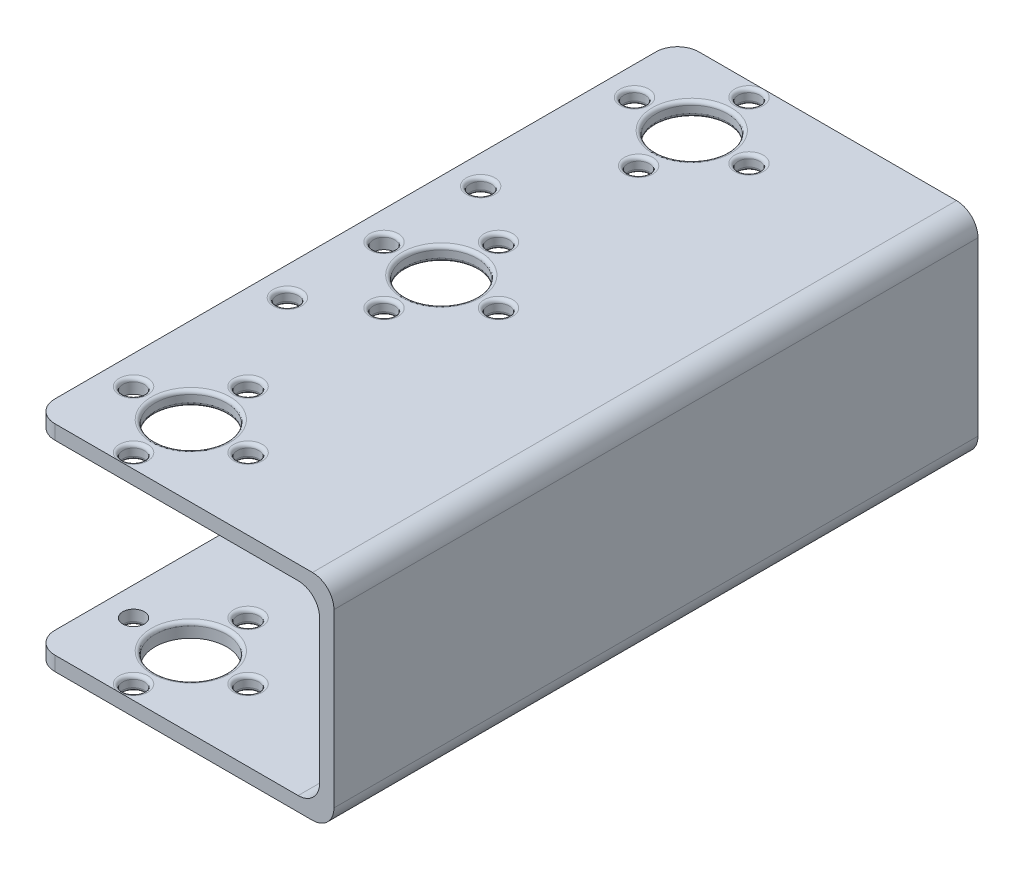
SolidWorks part; units mm, degrees
ref_plane "Front Plane" through (0, 0, 0) normal (0, 0, 1) x (1, 0, 0)
ref_plane "Top Plane" through (0, 0, 0) normal (0, 1, 0) x (1, 0, 0)
ref_plane "Right Plane" through (0, 0, 0) normal (1, 0, 0) x (0, 0, -1)
sketch "Sketch1" plane through (0, 0, 0) normal (0, 0, 1) x (1, 0, 0)
  line L0 (0, 0) -> (42, 0)
  line L1 (42, 0) -> (42, 30)
  line L2 (42, 30) -> (0, 30)
  line L3 (0, 2) -> (40, 2)
  line L4 (40, 2) -> (40, 28)
  line L5 (40, 28) -> (0, 28)
  line L6 (0, 30) -> (0, 28)
  line L7 (0, 2) -> (0, 0)
  dimension "D1" = 30
  dimension "D2" = 42
  dimension "D3" = 2
extrude "Boss-Extrude1" add sketch "Sketch1" along normal blind 90
sketch "Sketch2" plane through (0, 30, 0) normal (0, 1, 0) x (1, 0, 0)
  line L0 (42, -90) -> (42, 0) construction
  line L1 (0, -90) -> (0, 0) construction
  line L2 (12, -45) -> (4, -45) construction
  line L3 (12, -10) -> (4, -10) construction
  line L4 (12, -80) -> (4, -80) construction
  circle A0 centre (12, -45) radius 5
  circle A1 centre (4, -45) radius 1.5
  circle A2 centre (12, -37) radius 1.5
  circle A3 centre (20, -45) radius 1.5
  circle A4 centre (12, -53) radius 1.5
  circle A5 centre (12, -10) radius 5
  circle A6 centre (4, -10) radius 1.5
  circle A7 centre (12, -2) radius 1.5
  circle A8 centre (20, -10) radius 1.5
  circle A9 centre (12.5673, -18) radius 1.5
  circle A10 centre (12, -80) radius 5
  circle A11 centre (4, -80) radius 1.5
  circle A12 centre (12, -72) radius 1.5
  circle A13 centre (20, -80) radius 1.5
  circle A14 centre (12, -88) radius 1.5
  circle A15 centre (4, -31.5) radius 1.5
  circle A16 centre (4, -58.5) radius 1.5
  point P2 (0, 0)
  point P5 (42, -45)
  point P30 (0, 0)
  point P31 (0, 0)
  point P44 (0, 0)
  point P45 (0, 0)
  point P46 (22.2955, -82.3885)
  point P47 (12, -87.7409)
  point P48 (0, 0)
  point P49 (0, 0)
  point P52 (2.628, -29.4041)
  point P55 (2.628, -58.1751)
  point P56 (0, 0)
  point P57 (0, 0)
  dimension "D1" = 10
  dimension "D3" = 8
  dimension "0.3" = 3
  dimension "D6" = 8
  dimension "D7" = 10
  dimension "D10" = 10
  dimension "D2" = 12
  dimension "D5" = 8
  dimension "D8" = 8
  dimension "D9" = 8
  dimension "D11" = 8
  dimension "D12" = 8
  dimension "D13" = 35
  dimension "D14" = 8
  dimension "D15" = 8
  dimension "D16" = 35
  dimension "D17" = 8
  dimension "D18" = 8
  dimension "D19" = 13.5
  dimension "D20" = 13.5
  dimension "D4" = 4
extrude "Cut-Extrude1" cut sketch "Sketch2" against normal through all
fillet "Fillet1" radius 3 8 edges at (0, 1, 90) (0, 1, 0) (0, 29, 0) (0, 29, 90) (40, 28, 45) (40, 2, 45) (42, 0, 45) (42, 30, 45)
fillet "Fillet2" radius 0.5 63 edges at (12, 2, 75) (12, 2, 0.5) (10.5, 0, 2) (20, 2, 8.5) (18.5, 0, 10) (12, 2, 5) (7, 0, 10) (4, 2, 8.5) (2.5, 0, 10) (12.5673, 2, 16.5) (11.0673, 0, 18) (4, 2, 30) (2.5, 0, 31.5) (12, 2, 35.5) (10.5, 0, 37) (4, 2, 43.5) (2.5, 0, 45) (20, 2, 43.5) (18.5, 0, 45) (12, 2, 51.5) (10.5, 0, 53) (12, 2, 70.5) (10.5, 0, 72) (20, 2, 78.5) (18.5, 0, 80) (12, 2, 86.5) (10.5, 0, 88) (20, 28, 11.5) (18.5, 30, 10) (12, 28, 3.5) (10.5, 30, 2) (12, 28, 15) (7, 30, 10) (4, 28, 11.5) (2.5, 30, 10) (12.5673, 28, 19.5) (11.0673, 30, 18) (4, 28, 33) (2.5, 30, 31.5) (12, 28, 38.5) (10.5, 30, 37) (20, 28, 46.5) (18.5, 30, 45) (12, 28, 54.5) (10.5, 30, 53) (4, 28, 60) (2.5, 30, 58.5) (12, 28, 50) (7, 30, 45) (20, 28, 81.5) (18.5, 30, 80) (12, 28, 73.5) (10.5, 30, 72) (12, 28, 89.5) (10.5, 30, 88) (12, 28, 85) (7, 30, 80) (7, 0, 45) (12, 2, 40) (2.5, 0, 58.5) (2.5, 0, 80) (2.5, 30, 80) (2.5, 30, 45)
